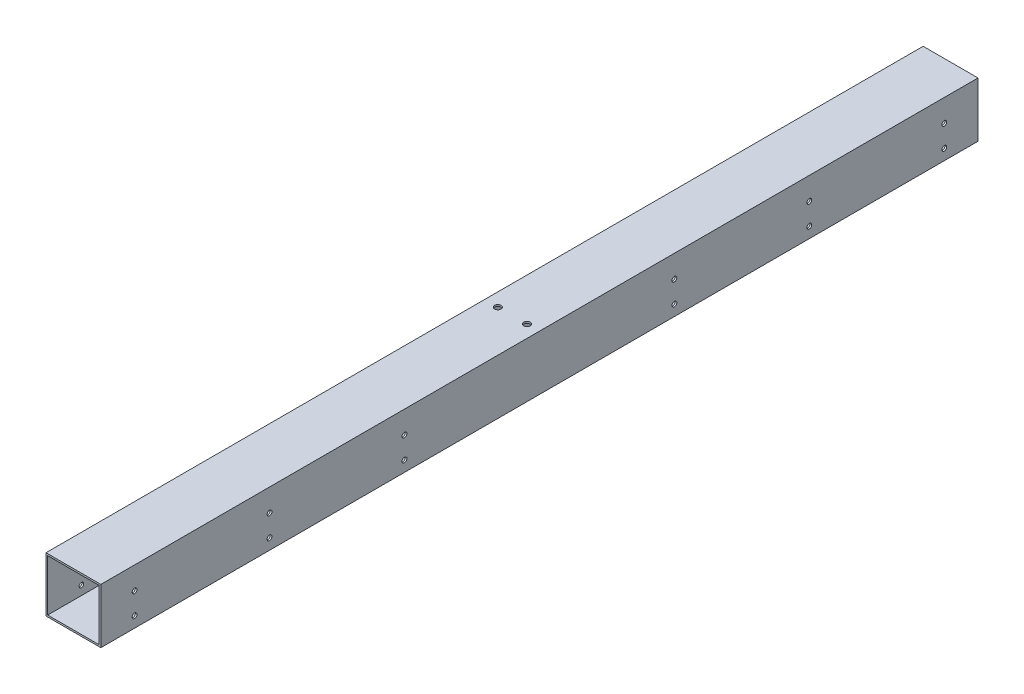
SolidWorks part; units mm, degrees
material "6063-T6"
ref_plane "Front Plane" through (0, 0, 0) normal (0, 0, 1) x (1, 0, 0)
ref_plane "Top Plane" through (0, 0, 0) normal (0, 1, 0) x (1, 0, 0)
ref_plane "Right Plane" through (0, 0, 0) normal (1, 0, 0) x (0, 0, -1)
sketch "Sketch1" plane through (0, 0, 0) normal (0, 0, 1) x (1, 0, 0)
  line L1 (-50.8, 50.8) -> (50.8, 50.8)
  line L2 (-50.8, 50.8) -> (-50.8, -50.8)
  line L3 (-50.8, -50.8) -> (50.8, -50.8)
  line L4 (50.8, 50.8) -> (50.8, -50.8)
  line L5 (-50.8, 50.8) -> (50.8, -50.8) construction
  line L6 (-50.8, -50.8) -> (50.8, 50.8) construction
  point P0 (0, 0)
  dimension "D1" = 101.6
extrude "Extrude-Thin1" add sketch "Sketch1" along normal mid plane 1625 thin thin type one direction reverse wall 3.175
hole_wizard "M8 Clearance Hole2" positions "Sketch2" profile "Sketch3" hole size "M8" standard "ANSI Metric" end condition up to next
sketch "Sketch2" plane through (-50.8, 0, 0) normal (-1, 0, 0) x (0, 0, 1)
  line L0 (750, 9.2) -> (750, -30.8)
  line L1 (750, -30.8) -> (750, -50.8)
  line L2 (812.5, -50.8) -> (-812.5, -50.8) construction
  point P0 (750, 9.2)
  point P2 (750, -30.8)
  dimension "D1" = 40
  dimension "D2" = 20
  dimension "D3" = 750
sketch "Sketch3" plane through (-50.8, 9.2, 750) normal (0, 1, 0) x (0, 0, 1)
  line L0 (0, 0) -> (0, 3.175)
  line L1 (0, 3.175) -> (4.2, 3.175)
  line L2 (4.2, 3.175) -> (4.2, 0)
  line L5 (4.2, 0) -> (0, 0)
  line L11 (0, -6.35) -> (0, 107.95) construction
  dimension "Thru Hole Dia." = 8.4
  dimension "Thru Hole Depth" = 3.175
hole_wizard "M8 Clearance Hole1" positions "Sketch4" profile "Sketch5" hole size "M8" standard "ANSI Metric" end condition up to next
sketch "Sketch4" plane through (47.625, 0, 0) normal (-1, 0, 0) x (0, 0, 1)
  point P0 (750, 9.2)
  point P3 (750, -30.8)
sketch "Sketch5" plane through (47.625, 9.2, 750) normal (0, 1, 0) x (0, 0, 1)
  line L0 (0, 0) -> (0, 3.175)
  line L1 (0, 3.175) -> (4.5, 3.175)
  line L2 (4.5, 3.175) -> (4.5, 0)
  line L5 (4.5, 0) -> (0, 0)
  line L11 (0, -6.35) -> (0, 107.95) construction
  dimension "Thru Hole Dia." = 9
  dimension "Thru Hole Depth" = 3.175
pattern_linear "LPattern1" count 7 spacing 250 along (0, 0, -1) skipping (3, 0) of "M8 Clearance Hole2", "M8 Clearance Hole1"
hole_wizard "Ø12.0 (12) Diameter Hole1" positions "Sketch6" profile "Sketch7" hole size "Ø12.0" standard "ANSI Metric" end condition up to next
sketch "Sketch6" plane through (0, 50.8, 0) normal (0, 1, 0) x (1, 0, 0)
  line L0 (27.8, 0) -> (-26.2, 0)
  line L2 (50.8, -812.5) -> (50.8, 812.5) construction
  point P0 (-26.2, 0)
  point P2 (27.8, 0)
  point P13 (0.8, 0)
  dimension "D1" = 54
  dimension "D2" = 50
  dimension "D3" = 0
sketch "Sketch7" plane through (-26.2, 50.8, 0) normal (1, 0, 0) x (0, 0, 1)
  line L0 (0, 0) -> (0, 3.175)
  line L1 (0, 3.175) -> (6, 3.175)
  line L2 (6, 3.175) -> (6, 0)
  line L5 (6, 0) -> (0, 0)
  line L11 (0, -6.35) -> (0, 107.95) construction
  dimension "Thru Hole Dia." = 12
  dimension "Thru Hole Depth" = 3.175
